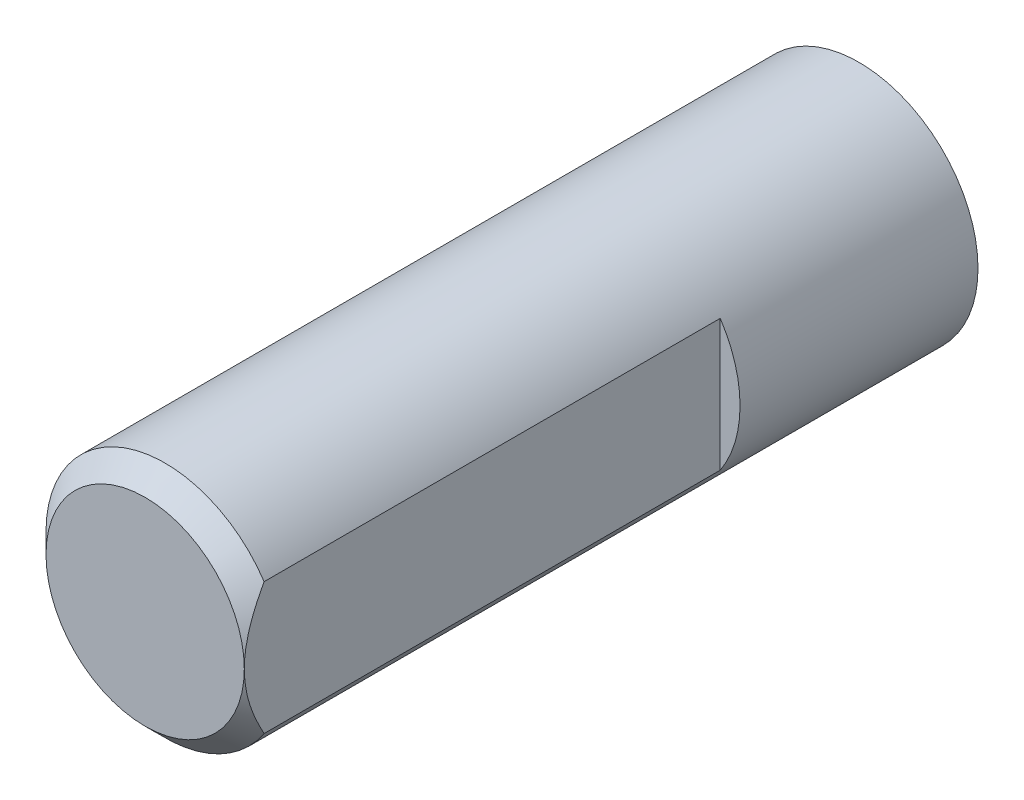
SolidWorks part; units mm, degrees
material "AISI 1020"
ref_plane "Front Plane" through (0, 0, 0) normal (0, 0, 1) x (1, 0, 0)
ref_plane "Top Plane" through (0, 0, 0) normal (0, 1, 0) x (1, 0, 0)
ref_plane "Right Plane" through (0, 0, 0) normal (1, 0, 0) x (0, 0, -1)
sketch "Sketch1" plane through (0, 0, 0) normal (0, 0, 1) x (1, 0, 0)
  circle A0 centre (0, 0) radius 3
  dimension "D1" = 6
extrude "Boss-Extrude1" add sketch "Sketch1" along normal blind 18
sketch "Sketch2" plane through (0, 0, 18) normal (0, 0, 1) x (1, 0, 0)
  line L0 (2.5, 1.6583) -> (2.5, -1.6583)
  line L1 (0, 0) -> (2.5, 0) construction
  line L2 (2.5, 0) -> (3, 0) construction
  circle A1 centre (0, 0) radius 3
  arc A2 (2.5, -1.6583) -> (2.5, 1.6583) centre (0, 0) ccw
  dimension "D2" = 0.5
  dimension "D1" = 0
extrude "Cut-Extrude1" cut sketch "Sketch2" against normal blind 12
chamfer "Chamfer1" distance 0.5 angle 45 1 edges at (-3, 0, 18)
